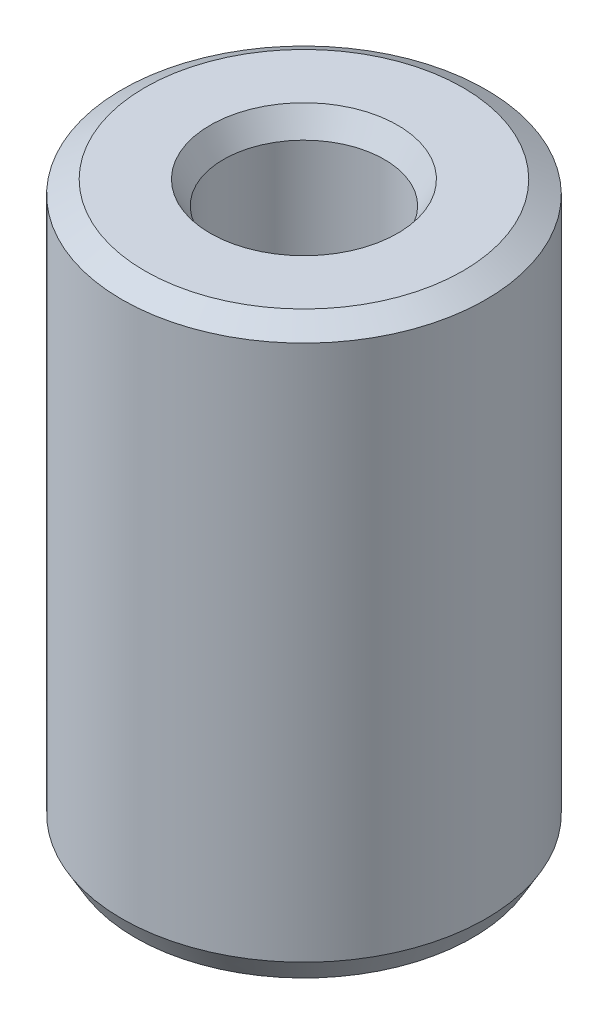
SolidWorks part; units mm, degrees
ref_plane "Front Plane" through (0, 0, 0) normal (0, 0, 1) x (1, 0, 0)
ref_plane "Top Plane" through (0, 0, 0) normal (0, 1, 0) x (1, 0, 0)
ref_plane "Right Plane" through (0, 0, 0) normal (1, 0, 0) x (0, 0, -1)
sketch "Sketch1" plane through (0, 0, 0) normal (0, 1, 0) x (1, 0, 0)
  circle A0 centre (0, 0) radius 47.5
  dimension "SLEEVE_OD" = 95
extrude "Boss-Extrude1" add sketch "Sketch1" along normal blind 149.4336
sketch "Sketch2" plane through (0, 0, 0) normal (0, 1, 0) x (1, 0, 0)
  circle A0 centre (0, 0) radius 20.9939
  dimension "BORE_D" = 41.9879
extrude "Cut-Extrude1" cut sketch "Sketch2" along normal through all
chamfer "Chamfer1" distance 3.4681 angle 60 4 edges at (0, 149.4336, 20.9939) (0, 0, 20.9939) (0, 0, 47.5) (0, 149.4336, 47.5) first distance on face at (0, 149.4336, 20.9939) first distance on face at (0, 0, 20.9939) first distance on face at (0, 149.4336, 47.5)
